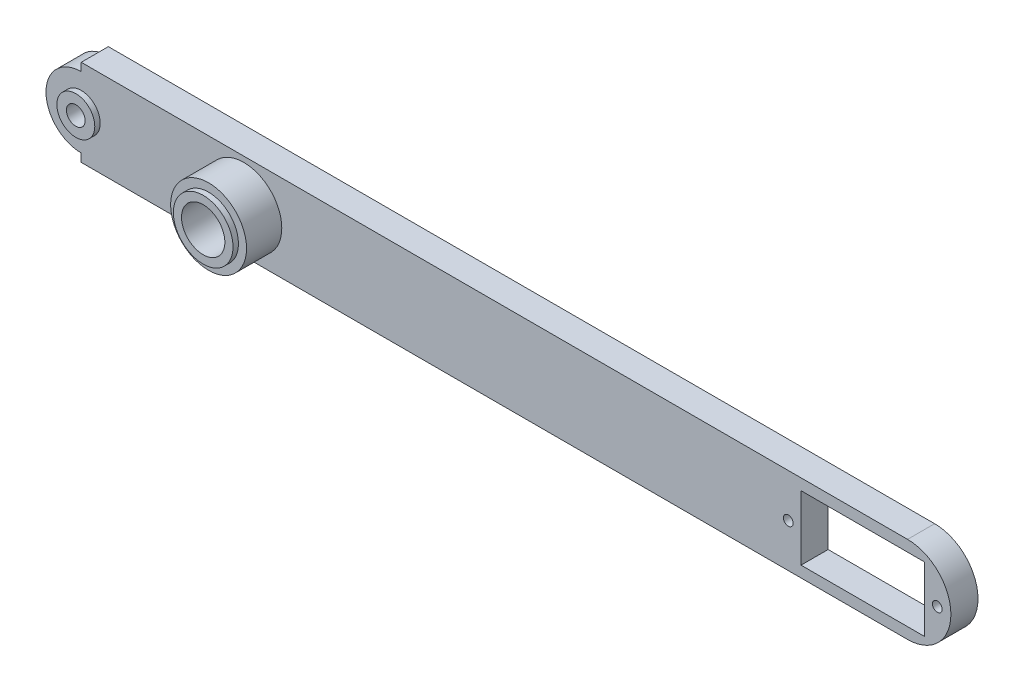
SolidWorks part; units mm, degrees
ref_plane "Front Plane" through (0, 0, 0) normal (0, 0, 1) x (1, 0, 0)
ref_plane "Top Plane" through (0, 0, 0) normal (0, 1, 0) x (1, 0, 0)
ref_plane "Right Plane" through (0, 0, 0) normal (1, 0, 0) x (0, 0, -1)
sketch "Sketch1" plane through (0, 0, 0) normal (0, 0, 1) x (1, 0, 0)
  line L0 (-30, -8) -> (122.45, -8)
  line L1 (122.45, -8) -> (122.45, 8)
  line L2 (122.45, 8) -> (-30, 8)
  line L3 (-30, 8) -> (-30, -8)
extrude "Boss-Extrude1" add sketch "Sketch1" along normal blind 5 from offset 9 offset against normal yes
sketch "Sketch2" plane through (0, 0, 0) normal (0, 0, 1) x (1, 0, 0)
  circle A0 centre (-30, 0) radius 6.5
extrude "Boss-Extrude2" add sketch "Sketch2" along normal blind 5 from offset 9 offset against normal yes
sketch "Sketch3" plane through (0, 0, 0) normal (0, 0, 1) x (1, 0, 0)
  circle A0 centre (122.45, 0) radius 8
extrude "Boss-Extrude3" add sketch "Sketch3" along normal blind 5 from offset 9 offset against normal yes
sketch "Sketch4" plane through (0, 0, 0) normal (0, 0, 1) x (1, 0, 0)
  circle A0 centre (0, 0) radius 7
extrude "Boss-Extrude4" add sketch "Sketch4" along normal blind 11.5 from offset 9 offset against normal yes
sketch "Sketch5" plane through (0, 0, 0) normal (0, 0, 1) x (1, 0, 0)
  circle A0 centre (0, 0) radius 5.5
extrude "Boss-Extrude5" add sketch "Sketch5" along normal blind 1 from offset 2.5
sketch "Sketch6" plane through (0, 0, 0) normal (0, 0, 1) x (1, 0, 0)
  circle A0 centre (-30, 0) radius 3.5
extrude "Boss-Extrude6" add sketch "Sketch6" along normal blind 1 from offset 4 offset against normal yes
sketch "Sketch7" plane through (0, 0, 0) normal (0, 0, 1) x (1, 0, 0)
  circle A0 centre (0, 0) radius 4
extrude "Cut-Extrude1" cut sketch "Sketch7" against normal through all and the other way through all
sketch "Sketch8" plane through (0, 0, 0) normal (0, 0, 1) x (1, 0, 0)
  circle A0 centre (-30, 0) radius 1.725
extrude "Cut-Extrude2" cut sketch "Sketch8" against normal through all and the other way through all
sketch "Sketch9" plane through (0, 0, 0) normal (0, 0, 1) x (1, 0, 0)
  line L0 (102.8, -5.95) -> (125.6, -5.95)
  line L1 (125.6, -5.95) -> (125.6, 5.95)
  line L2 (125.6, 5.95) -> (102.8, 5.95)
  line L3 (102.8, 5.95) -> (102.8, -5.95)
extrude "Cut-Extrude3" cut sketch "Sketch9" against normal through all and the other way through all
sketch "Sketch10" plane through (0, 0, 0) normal (0, 0, 1) x (1, 0, 0)
  circle A0 centre (100.45, 0) radius 0.9
  circle A1 centre (127.95, 0) radius 0.9
extrude "Cut-Extrude4" cut sketch "Sketch10" against normal through all and the other way through all
sketch "Sketch11" plane through (0, 0, 0) normal (0, 0, 1) x (1, 0, 0)
  circle A0 centre (40, 0) radius 2
  circle A1 centre (75, 0) radius 2
extrude "Cut-Extrude5" cut sketch "Sketch11" along normal blind 4 from offset 9 offset against normal yes
